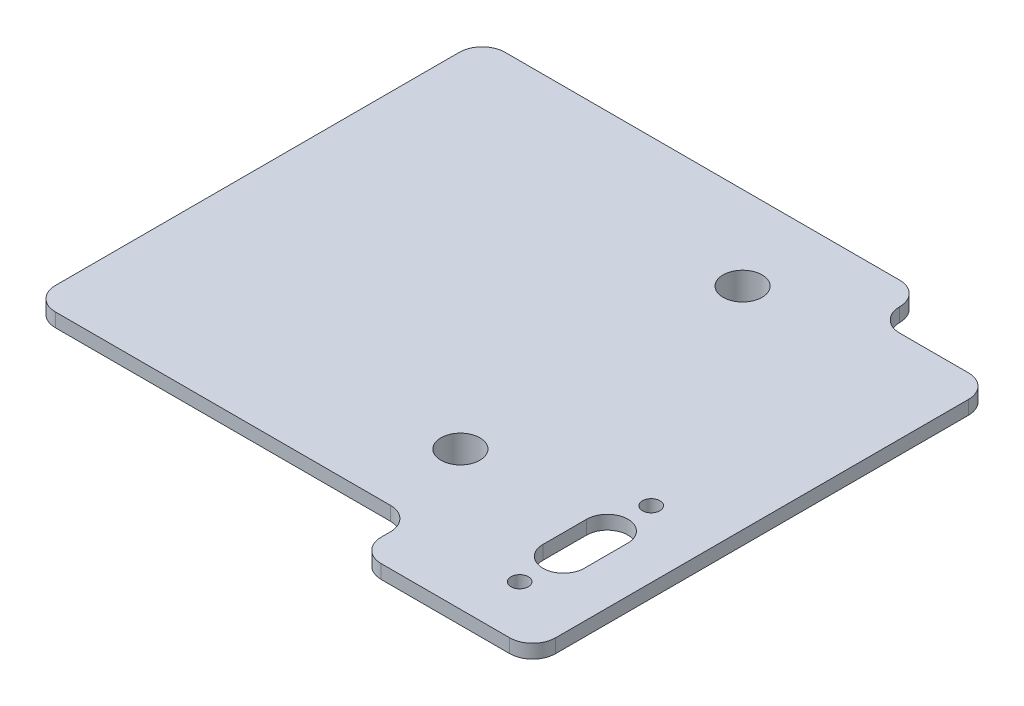
SolidWorks part; units mm, degrees
ref_plane "Front Plane" through (0, 0, 0) normal (0, 0, 1) x (1, 0, 0)
ref_plane "Top Plane" through (0, 0, 0) normal (0, 1, 0) x (1, 0, 0)
ref_plane "Right Plane" through (0, 0, 0) normal (1, 0, 0) x (0, 0, -1)
sketch "Sketch1" plane through (0, 0, 0) normal (0, 1, 0) x (1, 0, 0)
  line L0 (0, 0) -> (83, 0)
  line L1 (83, 0) -> (83, -12)
  line L2 (83, -12) -> (121, -12)
  line L3 (121, -12) -> (121, 88)
  line L5 (0, 98) -> (0, 0)
  line L6 (0, 49) -> (121, 49) construction
  line L7 (75, 79.75) -> (75, 18.25) construction
  line L8 (0, 98) -> (96, 98)
  line L9 (96, 98) -> (96, 88)
  line L10 (96, 88) -> (121, 88)
  point P11 (75, 49)
  point P13 (75, 79.75)
  point P14 (75, 18.25)
  point P17 (121, 88.7186)
  point P18 (0, 0)
  dimension "D1" = 121
  dimension "D2" = 110
  dimension "D3" = 38
  dimension "D4" = 12
  dimension "D5" = 61.5
  dimension "D6" = 8
  dimension "D7" = 10
  dimension "D8" = 25
extrude "plate" add sketch "Sketch1" along normal blind 3
sketch "Sketch2" plane through (0, 3, 0) normal (0, 1, 0) x (1, 0, 0)
  circle A0 centre (75, 79.75) radius 6
  circle A1 centre (75, 18.25) radius 6
  dimension "D1" = 12
extrude "mount posts" add sketch "Sketch2" against normal blind 22
sketch "Sketch3" plane through (0, 3, 0) normal (0, 1, 0) x (1, 0, 0)
  circle A0 centre (75, 79.75) radius 4.25
  circle A1 centre (75, 18.25) radius 4.25
  dimension "D1" = 8.5
extrude "mount cbore" cut sketch "Sketch3" against normal blind 19.5
hole_wizard "#8 Clearance Hole1" positions "Sketch4" profile "Sketch5" hole size "#8" standard "ANSI Inch" end condition through all
sketch "Sketch4" plane through (0, -16.5, 0) normal (0, 1, 0) x (1, 0, 0)
  circle A0 centre (75, 18.25) radius 4.25 construction
  circle A1 centre (75, 79.75) radius 4.25 construction
  point P0 (75, 79.75)
  point P2 (75, 18.25)
sketch "Sketch5" plane through (75, -16.5, -79.75) normal (1, 0, 0) x (0, 0, 1)
  line L0 (0, 0) -> (0, 2.5)
  line L1 (0, 2.5) -> (2.2479, 2.5)
  line L2 (2.2479, 2.5) -> (2.2479, 0)
  line L5 (2.2479, 0) -> (0, 0)
  line L11 (0, -6.35) -> (0, 107.95) construction
  dimension "Thru Hole Dia." = 4.4958
  dimension "Thru Hole Depth" = 2.5
ref_plane "mid plane" through (0, 0, -49) normal (0, 0, -1) x (1, 0, 0)
sketch "Sketch8" plane through (0, 0, -49) normal (0, 0, -1) x (1, 0, 0)
  line L0 (45.25, 0) -> (46.85, 0)
  line L1 (0, 0) -> (121, 0) construction
  line L2 (45.25, 0) -> (43.5, 29)
  line L3 (43.5, 29) -> (45.1, 29)
  line L4 (45.1, 29) -> (46.85, 0)
  line L5 (40, 0) -> (40, 41.9178) construction
  point P9 (44.3, 29)
  dimension "D1" = 1.6
  dimension "D2" = 3.5
  dimension "D3" = 29
  dimension "D4" = 5.25
  dimension "D5" = 40
revolve "foot" add sketch "Sketch8" angle 360 about L5
fillet "Fillet1" radius 1.5 2 edges at (40, 0, -43.75) (40, 0, -42.15)
sketch "Sketch7" plane through (0, 3, 0) normal (0, 1, 0) x (1, 0, 0)
  line L0 (106.5, 87.7375) -> (106.5, 106.2625) construction
  line L1 (121, -12) -> (121, 88) construction
  line L2 (83, -12) -> (121, -12) construction
  line L3 (115, 14) -> (98, 14) construction
  line L4 (102, 9.2375) -> (102, 18.7625)
  line L5 (98, -6) -> (98, 34) construction
  line L6 (98, -6) -> (115, -6) construction
  line L7 (115, -6) -> (115, 34) construction
  line L8 (98, 34) -> (115, 34) construction
  line L9 (98, -6) -> (115, 34) construction
  line L10 (115, -6) -> (98, 34) construction
  line L11 (111, 9.2375) -> (111, 18.7625)
  circle A0 centre (106.5, 9.2375) radius 4.5 construction
  circle A1 centre (106.5, 18.7625) radius 4.5 construction
  arc A2 (102, 9.2375) -> (111, 9.2375) centre (106.5, 9.2375) ccw
  arc A3 (102, 18.7625) -> (111, 18.7625) centre (106.5, 18.7625) cw
  circle A4 centre (106.5, 28.34) radius 1.9
  circle A5 centre (106.5, -0.34) radius 1.9
  point P16 (106.5, 14)
  point P19 (102, -12)
  dimension "D2" = 9.525
  dimension "D5" = 9
  dimension "D6" = 3.8
  dimension "D1" = 40
  dimension "D3" = 6
  dimension "D4" = 17
  dimension "D7" = 28.68
  dimension "D8" = 6
extrude "terminal strip" cut sketch "Sketch7" against normal through all
chamfer "Chamfer1" distance 3 angle 45 2 edges at (75, -16.5, -75.5) (75, -16.5, -14)
chamfer "Chamfer2" distance 1 angle 45 2 edges at (75, -19, -12.25) (75, -19, -73.75)
fillet "Fillet3" radius 1.5 2 edges at (75, 0, -73.75) (75, 0, -12.25)
fillet "corners" radius 5 8 edges at (0, 1.5, -98) (96, 1.5, -98) (96, 1.5, -88) (121, 1.5, -88) (121, 1.5, 12) (83, 1.5, 12) (83, 1.5, 0) (0, 1.5, 0)
